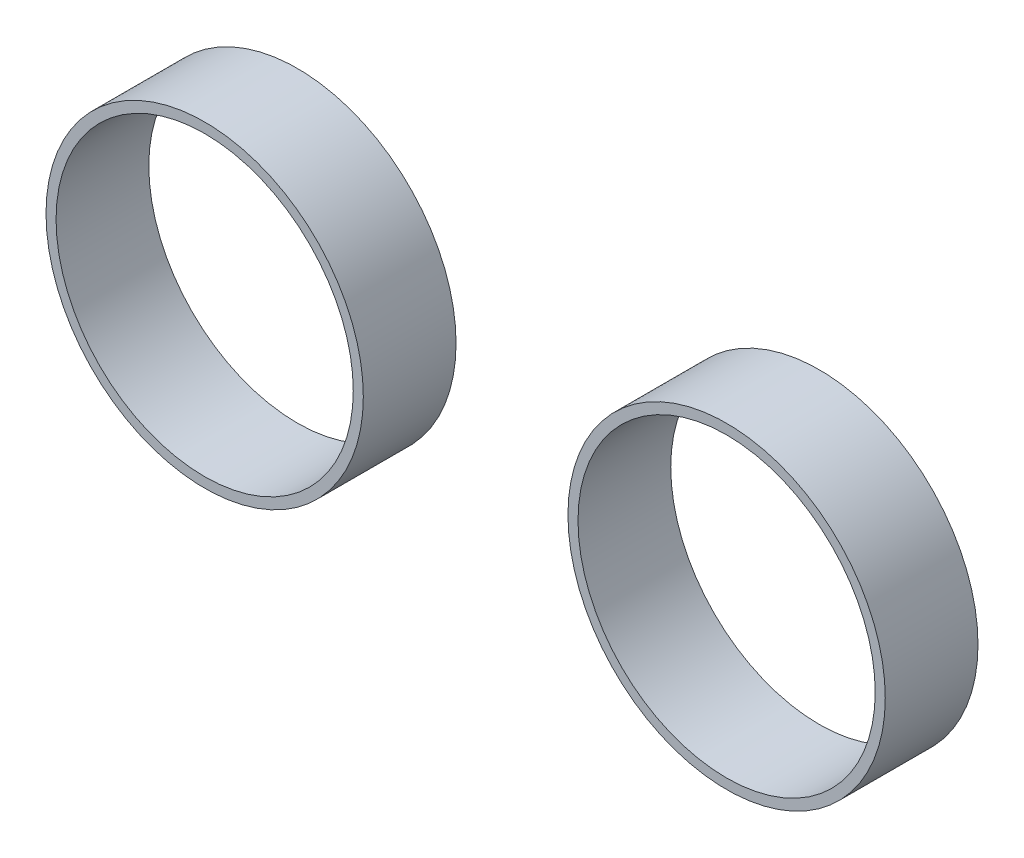
SolidWorks part; units mm, degrees
material "Velcro"
ref_plane "Front Plane" through (0, 0, 0) normal (0, 0, 1) x (1, 0, 0)
ref_plane "Top Plane" through (0, 0, 0) normal (0, 1, 0) x (1, 0, 0)
ref_plane "Right Plane" through (0, 0, 0) normal (1, 0, 0) x (0, 0, -1)
sketch "Sketch1" plane through (0, 0, 0) normal (0, 0, 1) x (1, 0, 0)
  circle A0 centre (1664.2805, -423.3823) radius 65 construction
  circle A1 centre (1664.2805, -423.3823) radius 69.4 construction
  circle A2 centre (1435.9805, -423.3823) radius 69.4 construction
  circle A3 centre (1435.9805, -423.3823) radius 65 construction
  circle A4 centre (1664.2805, -423.3823) radius 65
  circle A5 centre (1664.2805, -423.3823) radius 69.4
  circle A6 centre (1435.9805, -423.3823) radius 69.4
  circle A7 centre (1435.9805, -423.3823) radius 65
extrude "Boss-Extrude1" add sketch "Sketch1" along normal blind 40.56
